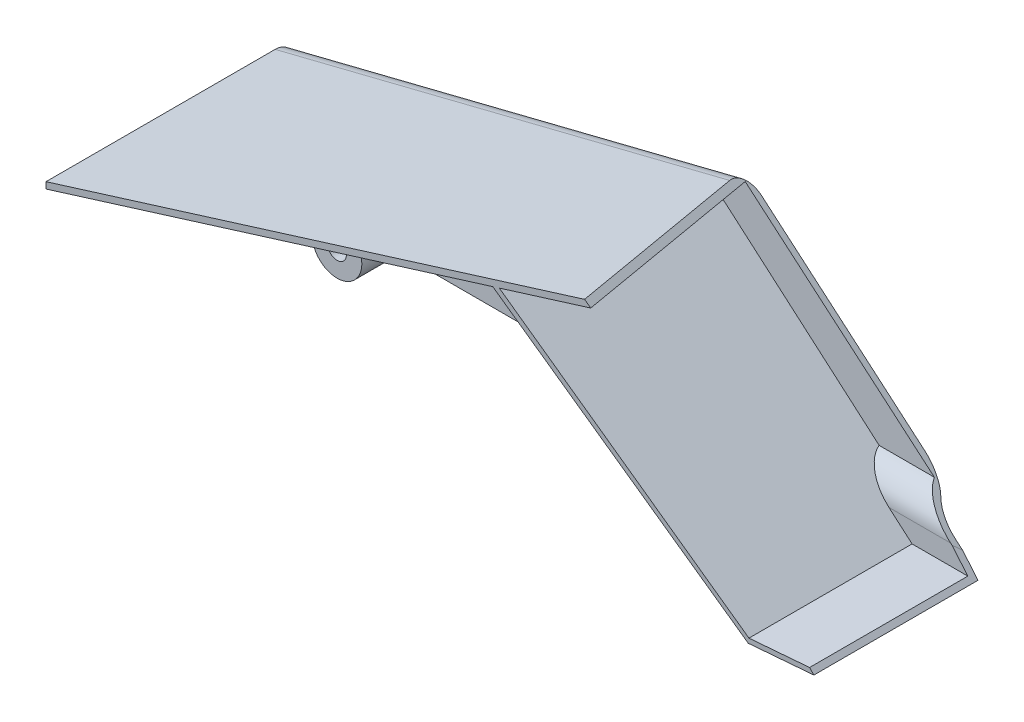
SolidWorks part; units mm, degrees
ref_plane "Piano frontale" through (0, 0, 0) normal (0, 0, 1) x (1, 0, 0)
ref_plane "Piano superiore" through (0, 0, 0) normal (0, 1, 0) x (1, 0, 0)
ref_plane "Piano destro" through (0, 0, 0) normal (1, 0, 0) x (0, 0, -1)
sketch "Schizzo1" plane through (0, 0, 0) normal (0, 0, 1) x (1, 0, 0)
  line L0 (-49, 0) -> (49, 0)
  line L1 (-49, 0) -> (-49, 5)
  line L2 (-49, 5) -> (-65, 5)
  line L3 (-65, 5) -> (-65, 17)
  line L4 (-65, 17) -> (17.4553, 37.6429)
  line L5 (17.4553, 37.6429) -> (49, 0)
  point P4 (0, 0)
  point P8 (2.9043, 34)
  dimension "D1" = 98
  dimension "D2" = 5
  dimension "D3" = 16
  dimension "D4" = 12
  dimension "D5" = 85
  dimension "D6" = 70
  dimension "D7" = 34
extrude "Estrusione-Estrusione1" add sketch "Schizzo1" along normal blind 40
sketch "Schizzo3" plane through (0, 0, 0) normal (1, 0, 0) x (0, 0, -1)
  line L0 (-3.5, 4) -> (-3.5, 0)
  line L1 (-40, 0) -> (0, 0) construction
  line L2 (-3.5, 0) -> (0, 0)
  line L3 (0, 0) -> (0, 0.5)
  line L4 (0, 0.5) -> (0, 7.5)
  arc A0 (0, 7.5) -> (-3.5, 4) centre (0, 4) ccw
  dimension "D1" = 7
  dimension "D2" = 4
extrude "Taglio-Estrusione1" cut sketch "Schizzo3" against normal through all both and the other way through all
shell "Svuota1" thickness 1 removed face at (0, 0, 21.75) removed face at (-49, 2.8011, 18.0781) removed face at (-57, 5, 21.6771) removed face at (-65, 10.4112, 16.7537) removed face at (-26.9241, 10.7738, 40) removed face at (36.7777, 14.5851, 14.6208)
sketch "Schizzo5" plane through (0, 0, 0) normal (0, 0, 1) x (1, 0, 0)
  line L0 (1.3224, 32.5731) -> (2.2925, 32.816)
  line L1 (18.1693, 36.7908) -> (-65, 15.9691) construction
  line L2 (2.2925, 32.816) -> (39.3577, 0.7665)
  line L3 (39.3577, 0.7665) -> (48.3577, 0.7665)
  line L4 (49, 0) -> (45.648, 4) construction
  line L5 (48.3577, 0.7665) -> (49, 0)
  line L6 (49, 0) -> (39.2565, 0)
  line L7 (-49, 0) -> (49, 0) construction
  line L8 (39.2565, 0) -> (1.3224, 32.5731)
  dimension "D1" = 1
  dimension "D2" = 1
  dimension "D3" = 49
  dimension "D4" = 50
  dimension "D5" = 9
extrude "Estrusione-Estrusione2" add sketch "Schizzo5" against normal up to body from surface separate body starting at face at (-23.5938, 26.8507, 40)
sketch "Schizzo8" plane through (0, 0, 0) normal (0, 0, 1) x (1, 0, 0)
  line L0 (-49, 4) -> (-49, 0) construction
  line L1 (-49, 0) -> (39.2565, 0) construction
  circle A0 centre (-45, 4) radius 4
  circle A1 centre (9, 4) radius 4
  dimension "D1" = 8
  dimension "D2" = 54
extrude "Estrusione-Estrusione3" add sketch "Schizzo8" against normal up to body from offset 13 separate body
sketch "Schizzo9" plane through (0, 0, 0) normal (0, 0, 1) x (1, 0, 0)
  circle A0 centre (-45, 4) radius 1.5
  circle A1 centre (9, 4) radius 1.5
  arc A2 (-49, 4) -> (-45, 0) centre (-45, 4) ccw construction
  dimension "D1" = 3
extrude "Taglio-Estrusione2" cut sketch "Schizzo9" against normal blind 30 from surface starting at face at (-41, 4, 13)
ref_plane "Piano1" through (-7.8386, 31.3105, 0) normal (-0.2429, 0.9701, 0) x (0.9701, 0.2429, 0)
sketch "Schizzo13" plane through (-7.8386, 31.3105, 0) normal (-0.2429, 0.9701, 0) x (0.9701, 0.2429, 0)
  line L1 (26.0745, 0) -> (-58.9255, 0) construction
  line L2 (16.0745, 0) -> (26.0745, 0)
  line L3 (26.0745, 0) -> (26.0745, -40)
  line L4 (26.0745, -40) -> (25.0745, -40)
  line L5 (26.0745, -40) -> (-58.9255, -40) construction
  line L6 (25.0745, -40) -> (16.0745, 0)
  dimension "D1" = 10
  dimension "D2" = 1
sketch "Schizzo17" plane through (0, 0, 0) normal (0, 0, 1) x (1, 0, 0)
  line L0 (7.7547, 35.2143) -> (60.9911, -10.2377)
  line L8 (17.4553, 37.6429) -> (-65, 17) construction
  dimension "D1" = 10
  dimension "D2" = 70
sweep "Taglia-Sweep3" cut profiles "Schizzo13" path "Schizzo17"
sketch "Schizzo18" plane through (0, 0, 0) normal (0, 1, 0) x (1, 0, 0)
  line L1 (-1, -3) -> (-12, -3)
  line L2 (-1, -3) -> (-1, -4)
  line L3 (-1, -4) -> (-12, -4)
  line L4 (-12, -3) -> (-12, -4)
  line L5 (5, -4.5) -> (5, -13) construction
  line L6 (-45, -4.5) -> (9, -4.5) construction
  point P6 (-1, -3.5)
  dimension "D1" = 1
  dimension "D2" = 11
  dimension "D3" = 6
  dimension "D4" = 0.5
extrude "Taglio-Estrusione3" cut sketch "Schizzo18" along normal blind 5
fillet "Raccordo1" radius 2 1 edges at (16.952, 37.0014, 40) type face fillet first side face at (31.2304, 17.569, 9.9493) second side face at (8.3491, 17.3894, 40)
fillet "Raccordo2" radius 3 1 edges at (-28.6227, 26.1071, 0) type face fillet first side face at (-18.398, 28.6669, 23.62) second side face at (-20.5075, 16.8036, 0)
fillet "Raccordo3" radius 4 1 edges at (-12.3923, 7.5, 0)
sketch "Schizzo22" plane through (0, 0, 0) normal (0, 1, 0) x (1, 0, 0)
  line L0 (-65, -40) -> (49, -30)
  line L1 (49, -40) -> (49, -3.5) construction
  line L2 (49, -30) -> (49, -40)
  line L4 (13.6272, -40) -> (49, -40)
  line L5 (13.6272, -40) -> (-65, -40) construction
  line L6 (13.6272, -40) -> (-65, -40)
  point P4 (0, 0)
  point P8 (0, 0)
  dimension "D2" = 10
extrude "Taglio-Estrusione4" cut sketch "Schizzo22" against normal blind 10 and the other way through all
